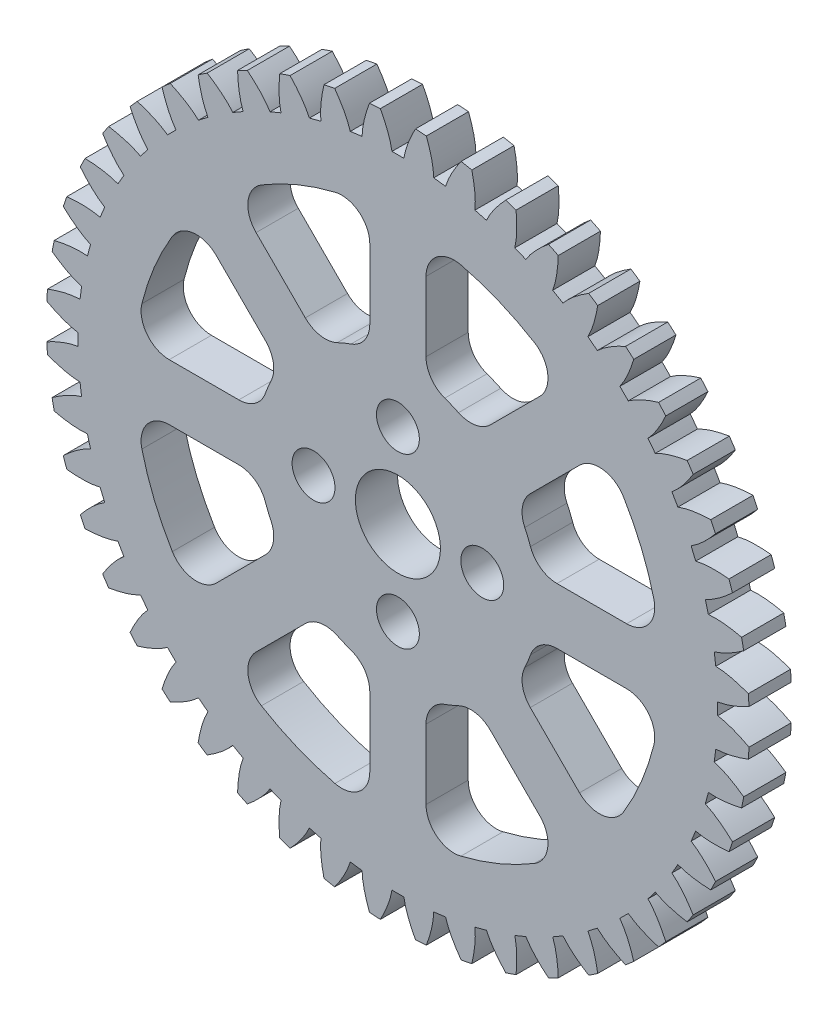
SolidWorks part; units mm, degrees
ref_plane "正面" through (0, 0, 0) normal (0, 0, 1) x (1, 0, 0)
ref_plane "平面" through (0, 0, 0) normal (0, 1, 0) x (1, 0, 0)
ref_plane "右側面" through (0, 0, 0) normal (1, 0, 0) x (0, 0, -1)
sketch "インボリュート スケッチ" plane through (0, 0, 0) normal (0, 0, 1) x (1, 0, 0)
  line L0 (-70.438, -23.8116) -> (0.4019, -22.549)
  line L1 (0.4019, -22.549) -> (-0.4019, 22.549) construction
  line L2 (0, 0) -> (0, 25) construction
  line L3 (-0.4019, 22.549) -> (-0.4054, 22.7464)
  line L4 (0, 0) -> (0.4019, -22.549)
  line L5 (-0.4054, 22.7464) -> (0, 22.7464)
  line L6 (0, 22.7464) -> (0, 0)
  circle A0 centre (0, 0) radius 22.5526 construction
  circle A1 centre (0, 0) radius 24 construction
  circle A2 centre (0, 0) radius 22.75 construction
  circle A3 centre (0, 0) radius 25 construction
  spline S0 degree 4 poles (-0.4019, 22.549) (-0.4043, 22.5919) (-0.4117, 22.6773) (-0.4369, 22.8471) (-0.4886, 23.0907) (-0.5628, 23.3644) (-0.6857, 23.7403) (-0.8782, 24.2318) (-1.1643, 24.8362) (-1.7417, 25.8497) (-2.6976, 27.1657) (-4.2523, 28.8251) (-6.5458, 30.6346) (-9.3246, 32.2398) (-12.5284, 33.5394) (-15.8665, 34.4327) (-19.283, 34.9432) (-22.9038, 35.1011) (-27.3837, 34.8283) (-32.6484, 33.82) (-38.5314, 31.7675) (-44.6351, 28.5052) (-49.5077, 24.9143) (-53.305, 21.3911) (-56.2012, 18.1959) (-58.352, 15.4987) (-60.3327, 12.6742) (-62.1401, 9.736) (-64.1797, 5.937) (-66.2726, 1.201) (-68.1932, -4.5312) (-69.3975, -10.0129) (-69.994, -14.2845) (-70.2598, -17.2892) (-70.355, -18.796) (-70.4098, -20.0849) (-70.4357, -21.0902) (-70.4466, -21.788) (-70.4498, -22.439) (-70.4494, -22.9528) (-70.4419, -23.6308) (-70.4328, -24.115) (-70.4123, -24.9069) (-70.3877, -25.5185) (-70.3541, -26.2633) (-70.3151, -26.928) (-70.2685, -27.6393) (-70.2157, -28.3236) (-70.1411, -29.1948) (-70.0385, -30.23) (-69.8993, -31.4416) (-69.7141, -32.8188) (-69.5557, -33.8513) (-69.4415, -34.5368) (-69.3823, -34.8798) knots 0 0 0 0 0 0.001401 0.002802 0.005604 0.008133 0.010661 0.015718 0.022839 0.02996 0.048734 0.068727 0.096889 0.125051 0.153212 0.181374 0.209535 0.237696 0.271429 0.327752 0.384075 0.440398 0.496721 0.524883 0.553044 0.581206 0.609367 0.637529 0.66569 0.722013 0.778336 0.834659 0.84874 0.86282 0.876901 0.883942 0.890982 0.895509 0.900036 0.904564 0.909091 0.914773 0.920455 0.926136 0.931818 0.9375 0.943182 0.948864 0.954545 0.965909 0.977273 0.988636 1 1 1 1 1 construction
  spline S1 degree 4 poles (-0.4019, 22.549) (-0.4043, 22.5919) (-0.4117, 22.6773) (-0.4369, 22.8471) (-0.4886, 23.0907) (-0.5628, 23.3644) (-0.6857, 23.7403) (-0.8782, 24.2318) (-1.1643, 24.8362) (-1.7417, 25.8497) (-2.6976, 27.1657) (-4.2523, 28.8251) (-6.5458, 30.6346) (-9.3246, 32.2398) (-12.5284, 33.5394) (-15.8665, 34.4327) (-19.283, 34.9432) (-22.9038, 35.1011) (-27.3837, 34.8283) (-32.6484, 33.82) (-38.5314, 31.7675) (-44.6351, 28.5052) (-49.5077, 24.9143) (-53.305, 21.3911) (-56.2012, 18.1959) (-58.352, 15.4987) (-60.3327, 12.6742) (-62.1401, 9.736) (-64.1797, 5.937) (-66.2726, 1.201) (-68.1932, -4.5312) (-69.3975, -10.0129) (-69.994, -14.2845) (-70.2598, -17.2892) (-70.355, -18.796) (-70.4098, -20.0849) (-70.4357, -21.0902) (-70.4466, -21.788) (-70.4498, -22.439) (-70.4494, -22.9528) (-70.4441, -23.4308) (-70.4403, -23.6856) (-70.438, -23.8116) knots 0 0 0 0 0 0.001401 0.002802 0.005604 0.008133 0.010661 0.015718 0.022839 0.02996 0.048734 0.068727 0.096889 0.125051 0.153212 0.181374 0.209535 0.237696 0.271429 0.327752 0.384075 0.440398 0.496721 0.524883 0.553044 0.581206 0.609367 0.637529 0.66569 0.722013 0.778336 0.834659 0.84874 0.86282 0.876901 0.883942 0.890982 0.895509 0.900036 0.904564 0.909091 0.909091 0.909091 0.909091 0.909091
  point P6 (-0.7853, 23.9872)
  point P12 (0, 24)
  point P24 (0, 0)
  dimension "D1" = 45.1052
  dimension "D2" = 48
  dimension "D3" = 45.5
  dimension "D4" = 50
  dimension "D5" = 0.7854
extrude "インボリュート ボス" add sketch "インボリュート スケッチ" along normal blind 3 contours S1 L0 L4 region at (-31.7048, 2.4995, 0)
mirror "インボリュート ミラー" about plane through (0, 0, 3) normal (1, 0, 0) of bodies 161
sketch "歯先円 スケッチ" plane through (0, 0, 3) normal (0, 0, 1) x (1, 0, 0)
  circle A0 centre (0, 0) radius 74.3539
  circle A1 centre (0, 0) radius 25
  dimension "D1" = 50
extrude "歯先円 カット" cut sketch "歯先円 スケッチ" against normal through all
sketch "歯分割 スケッチ" plane through (0, 0, 3) normal (0, 0, 1) x (1, 0, 0)
  line L0 (-1.6351, 24.9465) -> (0, 0)
  line L1 (0, 0) -> (1.6351, 24.9465)
  line L2 (0, 0) -> (0, 24) construction
  arc A0 (-1.6351, 24.9465) -> (1.6351, 24.9465) centre (0, 0) ccw
  circle A2 centre (0, 0) radius 24 construction
  arc A3 (-1.2492, 24.9688) -> (-10.3843, -22.7413) centre (0, 0) ccw construction
  point P9 (-1.5697, 23.9486)
  point P10 (1.5697, 23.9486)
  dimension "D1" = 48
  dimension "D2" = 3.1416
extrude "歯分割 カット" cut sketch "歯分割 スケッチ" against normal through all
pattern_circular "歯分割 円形コピー" count 48 over 360 about axis through (0, 0, 0) along (0, 0, 1) of bodies 166
sketch "歯底円 スケッチ" plane through (0, 0, 3) normal (0, 0, 1) x (1, 0, 0)
  circle A0 centre (0, 0) radius 22.75
  dimension "D1" = 45.5
extrude "歯底円 ボス" add sketch "歯底円 スケッチ" against normal through all
sketch "軸 丸穴 スケッチ" plane through (0, 0, 3) normal (0, 0, 1) x (1, 0, 0)
  circle A0 centre (0, 0) radius 3.025
  dimension "D1" = 6.05
extrude "軸 丸穴 カット" cut sketch "軸 丸穴 スケッチ" against normal through all
sketch "軸 キー溝 スケッチ" plane through (0, 0, 3) normal (0, 0, 1) x (1, 0, 0)
  line L2 (-1.5, 3.7081) -> (-1.5, 5.4)
  line L3 (-1.5, 5.4) -> (1.5, 5.4)
  line L4 (1.5, 3.7081) -> (1.5, 5.4)
  arc A0 (-1.5, 3.7081) -> (1.5, 3.7081) centre (0, 0) ccw
  dimension "D1" = 8
  dimension "D2" = 3
  dimension "D3" = 5.4
extrude "軸 キー溝 カット" [suppressed] cut sketch "軸 キー溝 スケッチ" against normal through all
sketch "軸 Dカット スケッチ" plane through (0, 0, 3) normal (0, 0, 1) x (1, 0, 0)
  line L0 (-2.3958, 3) -> (2.3958, 3)
  arc A0 (-2.828, 2.8289) -> (2.828, 2.8289) centre (0, 0) ccw
  arc A1 (-2.3958, 3) -> (-2.828, 2.8289) centre (-2.6458, 3) ccw
  arc A2 (2.828, 2.8289) -> (2.3958, 3) centre (2.6458, 3) ccw
  dimension "D1" = 8
  dimension "D3" = 0.5
  dimension "D2" = 3
extrude "軸 Dカット カット" [suppressed] cut sketch "軸 Dカット スケッチ" against normal through all
sketch "軸 角穴 スケッチ" plane through (0, 0, 3) normal (0, 0, 1) x (1, 0, 0)
  line L0 (-5.1, 5.1) -> (5.1, 5.1)
  line L1 (-5, -5) -> (5, -5) construction
  line L2 (-5, -5) -> (-5, 5) construction
  line L3 (-5, 5) -> (5, 5) construction
  line L4 (5, -5) -> (5, 5) construction
  line L5 (-5, -5) -> (5, 5) construction
  line L6 (-5, 5) -> (5, -5) construction
  line L7 (5.1, -5.1) -> (5.1, 5.1)
  line L8 (-5.1, -5.1) -> (5.1, -5.1)
  line L9 (-5.1, -5.1) -> (-5.1, 5.1)
  point P0 (0, 0)
  dimension "D1" = 10
  dimension "D2" = 0.1
extrude "軸 角穴 カット" [suppressed] cut sketch "軸 角穴 スケッチ" against normal through all
sketch "フランジ穴 スケッチ" plane through (0, 0, 3) normal (0, 0, 1) x (1, 0, 0)
  circle A0 centre (0, 12) radius 1.6
  circle A1 centre (12, 0) radius 1.6
  circle A2 centre (0, -12) radius 1.6
  circle A3 centre (-12, 0) radius 1.6
  point P12 (0, 0)
  dimension "D2" = 3.2
  dimension "D3" = 12
  dimension "D1" = 4
extrude "フランジ穴 カット" [suppressed] cut sketch "フランジ穴 スケッチ" against normal through all
sketch "合致用スケッチ" plane through (0, 0, 3) normal (0, 0, 1) x (1, 0, 0)
  line L0 (0, 0) -> (0, 24)
  line L1 (0, 0) -> (1.5697, 23.9486)
  circle A2 centre (0, 0) radius 24
  dimension "D1" = 48
  dimension "D2" = 3.75
sketch "ｽｹｯﾁ1" plane through (0, 0, 0) normal (0, 0, -1) x (-1, 0, 0)
  line L0 (0, 0) -> (0, 24) construction
  circle A0 centre (0, 6) radius 1.525
  circle A1 centre (6, 0) radius 1.525
  circle A2 centre (0, -6) radius 1.525
  circle A3 centre (-6, 0) radius 1.525
  point P14 (0, 0)
  dimension "D1" = 6
  dimension "D2" = 3.05
  dimension "D3" = 4
extrude "ｶｯﾄ - 押し出し1" cut sketch "ｽｹｯﾁ1" against normal through all
chamfer "面取り1" [suppressed] distance 1.75 angle 45
sketch "ｽｹｯﾁ2" plane through (0, 0, 3) normal (0, 0, 1) x (1, 0, 0)
  line L0 (0, 0) -> (0, -22.7464) construction
  line L1 (-0.4054, -22.7464) -> (0.4054, -22.7464) construction
  line L2 (0, 0) -> (-16.0841, -16.0841) construction
  line L3 (0, 0) -> (-22.7464, 0) construction
  line L4 (0, 0) -> (-16.0841, 16.0841) construction
  line L5 (0, 0) -> (0, 22.7464) construction
  line L6 (0, 0) -> (16.0841, 16.0841) construction
  line L7 (0, 0) -> (22.7464, 0) construction
  line L8 (0, 0) -> (16.0841, -16.0841) construction
  line L9 (-5.514, -8.3424) -> (-11.7684, -14.5968)
  line L10 (-2, -18.643) -> (-2, -9.798)
  line L11 (-14.5968, -11.7684) -> (-8.3424, -5.514)
  line L12 (-9.798, -2) -> (-18.643, -2)
  line L13 (-18.643, 2) -> (-9.798, 2)
  line L14 (-8.3424, 5.514) -> (-14.5968, 11.7684)
  line L15 (-11.7684, 14.5968) -> (-5.514, 8.3424)
  line L16 (-2, 9.798) -> (-2, 18.643)
  line L17 (2, 18.643) -> (2, 9.798)
  line L18 (5.514, 8.3424) -> (11.7684, 14.5968)
  line L19 (14.5968, 11.7684) -> (8.3424, 5.514)
  line L20 (9.798, 2) -> (18.643, 2)
  line L21 (18.643, -2) -> (9.798, -2)
  line L22 (8.3424, -5.514) -> (14.5968, -11.7684)
  line L23 (11.7684, -14.5968) -> (5.514, -8.3424)
  line L24 (2, -9.798) -> (2, -18.643)
  arc A0 (-2, -9.798) -> (-5.514, -8.3424) centre (0, 0) cw
  arc A1 (-2, -18.643) -> (-11.7684, -14.5968) centre (0, 0) cw
  arc A2 (-8.3424, -5.514) -> (-9.798, -2) centre (0, 0) cw
  arc A3 (-14.5968, -11.7684) -> (-18.643, -2) centre (0, 0) cw
  arc A4 (-9.798, 2) -> (-8.3424, 5.514) centre (0, 0) cw
  arc A5 (-18.643, 2) -> (-14.5968, 11.7684) centre (0, 0) cw
  arc A6 (-5.514, 8.3424) -> (-2, 9.798) centre (0, 0) cw
  arc A7 (-11.7684, 14.5968) -> (-2, 18.643) centre (0, 0) cw
  arc A8 (2, 9.798) -> (5.514, 8.3424) centre (0, 0) cw
  arc A9 (2, 18.643) -> (11.7684, 14.5968) centre (0, 0) cw
  arc A10 (8.3424, 5.514) -> (9.798, 2) centre (0, 0) cw
  arc A11 (14.5968, 11.7684) -> (18.643, 2) centre (0, 0) cw
  arc A12 (9.798, -2) -> (8.3424, -5.514) centre (0, 0) cw
  arc A13 (18.643, -2) -> (14.5968, -11.7684) centre (0, 0) cw
  arc A14 (5.514, -8.3424) -> (2, -9.798) centre (0, 0) cw
  arc A15 (11.7684, -14.5968) -> (2, -18.643) centre (0, 0) cw
  point P14 (0, 0)
  point P47 (0, 0)
  dimension "D2" = 10
  dimension "D3" = 18.75
  dimension "D4" = 2
  dimension "D5" = 2
  dimension "D1" = 8
  dimension "D6" = 8
extrude "ｶｯﾄ - 押し出し2" cut sketch "ｽｹｯﾁ2" against normal through all
fillet "ﾌｨﾚｯﾄ1" radius 2 32 edges at (-2, -18.643, 1.5) (-11.7684, -14.5968, 1.5) (-5.514, -8.3424, 1.5) (-2, -9.798, 1.5) (14.5968, 11.7684, 1.5) (18.643, 2, 1.5) (9.798, 2, 1.5) (8.3424, 5.514, 1.5) (18.643, -2, 1.5) (14.5968, -11.7684, 1.5) (8.3424, -5.514, 1.5) (9.798, -2, 1.5) (11.7684, -14.5968, 1.5) (2, -18.643, 1.5) (2, -9.798, 1.5) (5.514, -8.3424, 1.5) (-14.5968, -11.7684, 1.5) (-18.643, -2, 1.5) (-9.798, -2, 1.5) (-8.3424, -5.514, 1.5) (-18.643, 2, 1.5) (-14.5968, 11.7684, 1.5) (-8.3424, 5.514, 1.5) (-9.798, 2, 1.5) (-11.7684, 14.5968, 1.5) (-2, 9.798, 1.5) (-5.514, 8.3424, 1.5) (2, 18.643, 1.5) (11.7684, 14.5968, 1.5) (5.514, 8.3424, 1.5) (2, 9.798, 1.5) (-2, 18.643, 1.5)
equation "\"モジュール\"= 1."
equation "\"基準圧力角\"= 20"
equation "\"歯数\"= 48"
equation "\"基準円直径\"= \"歯数\" * \"モジュール\""
equation "\"基礎円直径\"= \"基準円直径\" * cos ( \"基準圧力角\" )"
equation "\"歯先円直径\"= \"基準円直径\" + 2 * \"モジュール\""
equation "\"歯底円直径\"= \"基準円直径\" - 2.5 * \"モジュール\""
equation "\"D1@インボリュート スケッチ\" = \"基礎円直径\""
equation "\"D2@インボリュート スケッチ\" = \"基準円直径\""
equation "\"D3@インボリュート スケッチ\" = \"歯底円直径\""
equation "\"D4@インボリュート スケッチ\" = \"歯先円直径\""
equation "\"D5@インボリュート スケッチ\" = Pi * \"モジュール\" / 4"
equation "\"D1@歯先円 スケッチ\" = \"歯先円直径\""
equation "\"D1@歯分割 スケッチ\" = \"基準円直径\""
equation "\"D2@歯分割 スケッチ\" = PI * \"モジュール\""
equation "\"D1@歯分割 円形コピー\" = \"歯数\""
equation "\"D1@歯底円 スケッチ\" = \"歯底円直径\""
equation "\"板厚\"= 3"
equation "\"D1@インボリュート ボス\"=\"板厚\""
equation "\"D1@合致用スケッチ\" = \"基準円直径\""
equation "\"D2@合致用スケッチ\"=180/\"歯数\""
